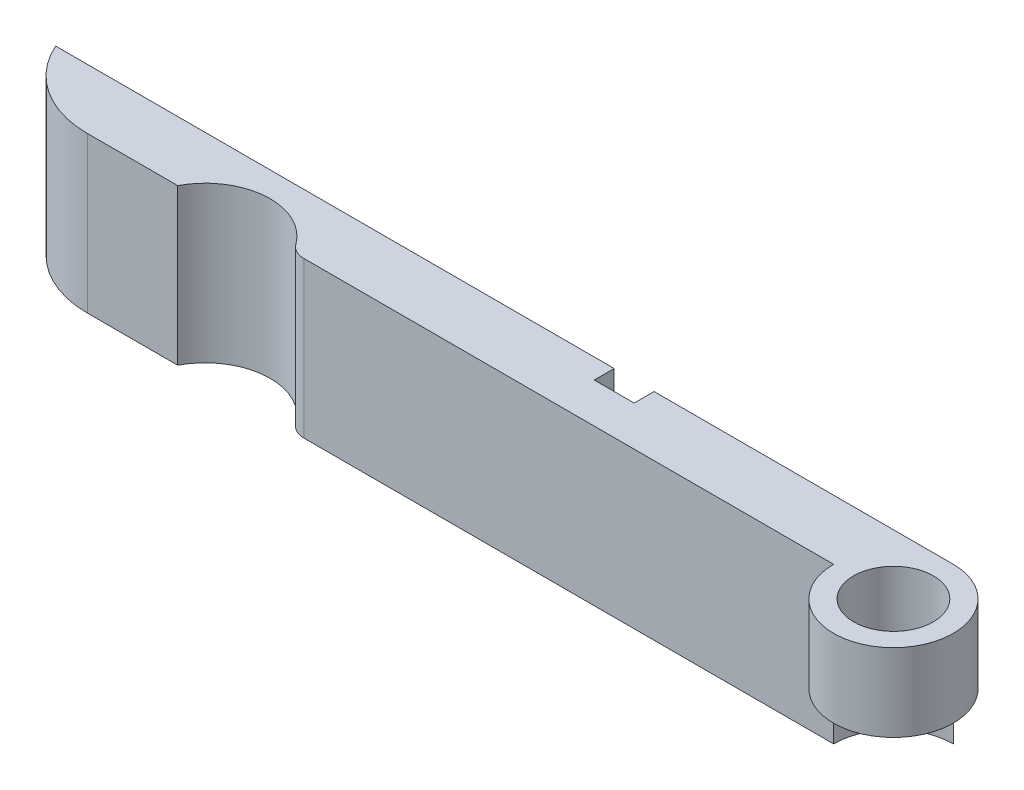
SolidWorks part; units mm, degrees
ref_plane "Alzado" through (0, 0, 0) normal (0, 0, 1) x (1, 0, 0)
ref_plane "Planta" through (0, 0, 0) normal (0, 1, 0) x (1, 0, 0)
ref_plane "Vista lateral" through (0, 0, 0) normal (1, 0, 0) x (0, 0, -1)
sketch "Croquis1" plane through (0, 0, 0) normal (0, 1, 0) x (1, 0, 0)
  circle A0 centre (0, 0) radius 3
  circle A1 centre (0, 0) radius 2
  dimension "D1" = 6
  dimension "D2" = 4
extrude "Saliente-Extruir1" add sketch "Croquis1" along normal blind 3.9
sketch "Croquis2" plane through (0, 0, 0) normal (0, -1, 0) x (1, 0, 0)
  line L0 (0, 3.7949) -> (0, 3) construction
  line L1 (0, -3) -> (-45, -3)
  line L2 (-45, -3) -> (-45, 0)
  line L3 (-45, 0) -> (-3, 0)
  line L5 (0, -3) -> (0, -4.2431) construction
  circle A0 centre (0, 0) radius 3
  circle M5 centre (0, 0) radius 3
  dimension "D2" = 6
  dimension "D1" = 3
  dimension "D3" = 45
extrude "Saliente-Extruir2" add sketch "Croquis2" along normal blind 3.9 and the other way blind 3.9 contours L3 L2 L1 M5 region at (-23.6728, 0, -1.5125)
fillet "Redondeo1" radius 5 1 edges at (-45, 0, 0)
sketch "Croquis3" plane through (0, -3.9, 0) normal (0, -1, 0) x (1, 0, 0)
  line L0 (0, -3) -> (-45, -3) construction
  line L1 (-17, -2) -> (-15, -2)
  line L2 (-17, -2) -> (-17, -4)
  line L3 (-17, -4) -> (-15, -4)
  line L4 (-15, -2) -> (-15, -4)
  line L5 (-17, -2) -> (-15, -4) construction
  line L6 (-17, -4) -> (-15, -2) construction
  line L7 (0, -9.4284) -> (0, 7.644) construction
  point P0 (-16, -3)
  dimension "D1" = 2
  dimension "D2" = 2
  dimension "D3" = 15
extrude "Cortar-Extruir1" cut sketch "Croquis3" against normal through all
sketch "Croquis4" plane through (0, -3.9, 0) normal (0, -1, 0) x (1, 0, 0)
  line L0 (-40.4174, 0) -> (-3, 0) construction
  circle A0 centre (-33, 1.5) radius 3.25
  dimension "D1" = 6.5
  dimension "D2" = 1.5
  dimension "D3" = 33
extrude "Cortar-Extruir2" cut sketch "Croquis4" against normal through all
fillet "Redondeo2" radius 1 1 edges at (-30.1169, 0, 0)
